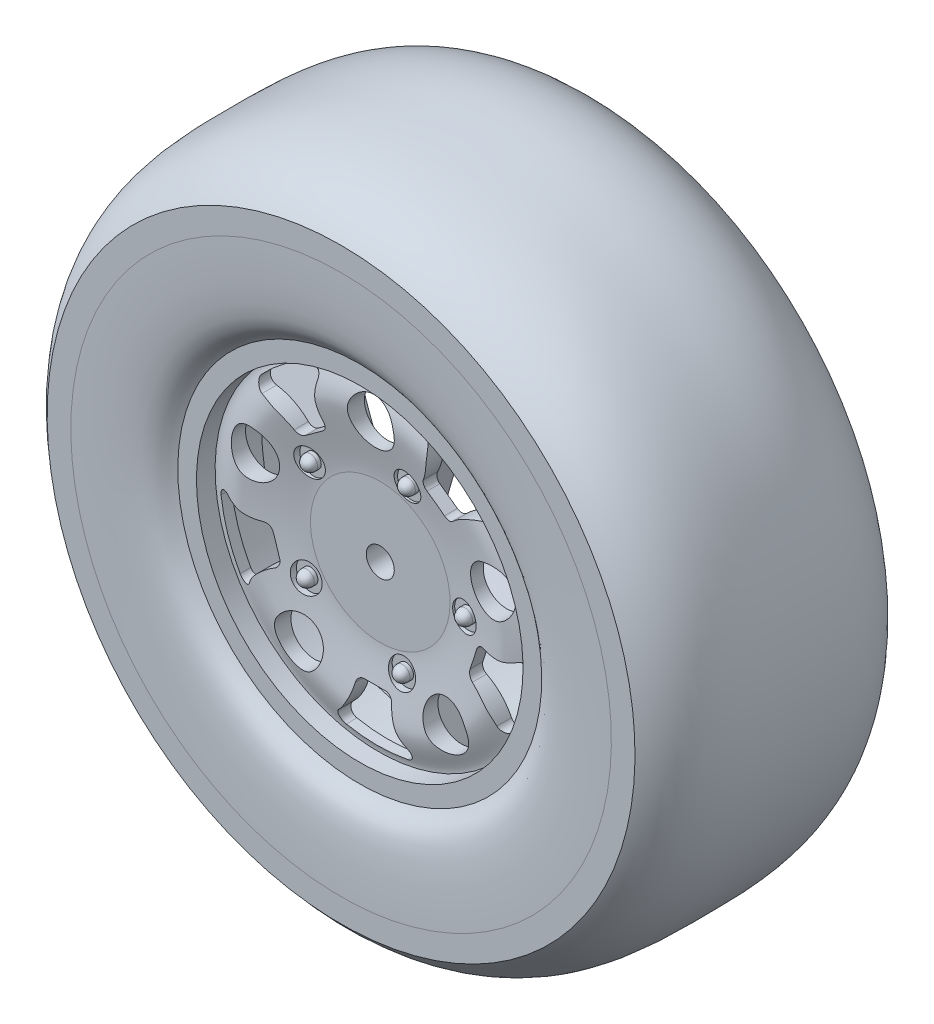
SolidWorks part; units mm, degrees
ref_plane "Front Plane" through (0, 0, 0) normal (0, 0, 1) x (1, 0, 0)
ref_plane "Top Plane" through (0, 0, 0) normal (0, 1, 0) x (1, 0, 0)
ref_plane "Right Plane" through (0, 0, 0) normal (1, 0, 0) x (0, 0, -1)
sketch "Sketch1" plane through (0, 0, 0) normal (1, 0, 0) x (0, 0, -1)
  line L0 (-21.4313, 50.0062) -> (-21.4312, 0)
  line L1 (21.4312, 0) -> (21.4312, 50.0062)
  line L2 (-17.514, 53.4656) -> (17.514, 53.4656) construction
  line L3 (21.4312, 0) -> (-21.4312, 0)
  line L4 (-21.4312, 10.75) -> (21.4312, 10.75) construction
  line L5 (0, 10.75) -> (0, 53.4656) construction
  line L6 (21.4312, 50.0062) -> (26.3997, 50.0062) construction
  line L7 (-18.2562, 30.9562) -> (-18.2562, 27.7812)
  line L8 (-18.2562, 27.7812) -> (-15.0812, 27.7812)
  line L9 (-14.7637, 0) -> (-14.7637, 11.8769)
  line L10 (-14.7637, 2.3812) -> (21.4312, 2.3812)
  line L11 (19.8438, 42.0687) -> (19.8438, 38.8937)
  line L12 (19.8438, 38.8937) -> (-13.4937, 38.8937)
  line L13 (-13.4937, 38.8937) -> (-13.4937, 30.9562)
  line L14 (-13.4937, 30.9562) -> (-5.5562, 30.9562)
  line L15 (-5.5562, 30.9562) -> (-5.5562, 29.3687)
  line L16 (-5.5562, 29.3687) -> (-13.4937, 29.3687)
  line L17 (-13.4937, 29.3687) -> (-13.4937, 5.5562)
  line L18 (-13.4937, 5.5562) -> (-5.5562, 5.5562)
  line L19 (-5.5562, 5.5562) -> (-5.5562, 2.3812)
  spline S0 degree 3 poles (-21.4312, 50.0062) (-16.3365, 56.4478) (0, 56.2647) (16.3365, 56.4478) (21.4312, 50.0062) knots 0 0 0 0 0.5 1 1 1 1
  spline S1 degree 3 poles (-21.4312, 50.0062) (-21.5438, 32.2009) (-20.2763, 33.9382) (-18.2562, 30.9562) knots 0 0 0 0 1 1 1 1
  spline S2 degree 3 poles (-15.0812, 27.7812) (-15.1289, 26.6155) (-16.3602, 24.649) (-16.5049, 21.0048) (-14.8841, 14.5257) (-14.7637, 11.8769) knots 0 0 0 0 0.567974 0.667974 1 1 1 1
  spline S3 degree 3 poles (21.4312, 50.0062) (21.4587, 44.8476) (21.3092, 43.9242) (19.8438, 42.0687) knots 0 0 0 0 1 1 1 1
  dimension "D6" = 19.05
  dimension "D1" = 42.8625
  dimension "D2" = 3.9172
  dimension "D3" = 50.0062
  dimension "D4" = 56.3562
  dimension "D5" = 3.175
  dimension "D7" = 3.175
  dimension "D8" = 3.175
  dimension "D9" = 6.6675
  dimension "D10" = 2.3813
  dimension "D11" = 7.9375
  dimension "D12" = 1.5875
  dimension "D13" = 3.175
  dimension "D14" = 34.925
  dimension "D15" = 1.5875
  dimension "D16" = 7.9375
  dimension "D17" = 5.5562
revolve "Revolve1" add sketch "Sketch1" angle 360 about L3 region at (0, 42.7852, 2.7909)
sketch "Sketch2" plane through (0, 0, 0) normal (0, 0, 1) x (1, 0, 0)
  line L0 (8.8735, 15.3386) -> (11.8459, 13.1791)
  line L1 (10.3597, 14.2588) -> (0, 0) construction
  line L2 (0, 0) -> (0, 9.3337) construction
  line L3 (-12.4986, -17.2029) -> (12.4986, -17.2029) construction
  line L4 (0, 0) -> (20.2232, 6.5709) construction
  circle A0 centre (0, 21.2639) radius 3.9688
  circle A1 centre (20.2232, 6.5709) radius 3.9688
  circle A2 centre (12.4986, -17.2029) radius 3.9688
  circle A3 centre (-12.4986, -17.2029) radius 3.9688
  circle A4 centre (-20.2232, 6.5709) radius 3.9688
  arc A5 (8.4882, 16.9423) -> (9.3812, 22.9129) centre (0, 21.2639) ccw
  arc A6 (11.1644, 3.6275) -> (26.7262, -0.3887) centre (20.2232, 6.5709) ccw
  arc A7 (19.6486, 18.121) -> (11.1624, 24.2867) centre (0, 0) ccw
  arc A8 (-8.6285, 25.298) -> (26.7262, -0.3887) centre (0, 0) ccw
  arc A9 (18.8925, 16.0025) -> (13.4901, 13.3082) centre (20.2232, 6.5709) ccw
  arc A10 (9.3812, 22.9129) -> (11.1624, 24.2867) centre (10.632, 23.1327) cw
  arc A11 (19.6486, 18.121) -> (18.8925, 16.0025) centre (18.7151, 17.26) cw
  arc A12 (13.4901, 13.3082) -> (11.8459, 13.1791) centre (12.5923, 14.2065) cw
  arc A13 (8.8735, 15.3386) -> (8.4882, 16.9423) centre (9.6199, 16.3661) cw
  point P25 (21.3935, 16.0237)
  dimension "D1" = 7.9375
  dimension "D3" = 19.05
  dimension "D4" = 19.05
  dimension "D8" = 1.27
  dimension "D5" = 72
  dimension "D6" = 36
  dimension "D7" = 21.2639
  dimension "D2" = 5
extrude "Cut-Extrude5" cut sketch "Sketch2" along normal up to surface (21.4312 mm away) contours A13 L0 A12 A9 A11 A7 A10 A5 | A0 region at (13.3756, 18.41, 0) region at (0, 21.2639, 0) up to face at (0, 45.9805, 21.4313)
ref_axis "Axis1" through (0, 0, -23.5744) along (0, 0, 1)
pattern_circular "CirPattern1" count 5 over 360 about axis through (0, 0, -23.5744) along (0, 0, 1) of "Cut-Extrude5"
sketch "Sketch5" plane through (0, 0, 14.7638) normal (0, 0, 1) x (1, 0, 0)
  line L0 (0.5332, 3.2628) -> (1.2955, 3.0417)
  line L1 (1.2955, 3.0417) -> (13.9237, 46.5782)
  line L2 (0.5332, 3.2628) -> (13.2791, 47.2052)
  line L3 (13.2791, 47.2052) -> (13.9237, 46.5782)
  line L5 (0.9143, 3.1523) -> (2.5178, 8.6803) construction
  dimension "D1" = 0.7937
extrude "Boss-Extrude2" add sketch "Sketch5" against normal up to surface (9.2075 mm away) up to face at (0, 29.3687, 5.5562)
pattern_circular "CirPattern2" count 5 over 360 about axis through (0, 0, -23.5744) along (0, 0, 1) of "Boss-Extrude2"
sketch "Sketch6" plane through (0, 0, 18.2562) normal (0, 0, 1) x (1, 0, 0)
  circle A0 centre (5.0132, 13.8528) radius 2.3812
  point P2 (0, 0)
  dimension "D1" = 4.7625
  dimension "D2" = 14.732
extrude "Cut-Extrude6" cut sketch "Sketch6" against normal blind 3.81
ref_axis "Axis2" through (5.0132, 13.8528, 14.4462) along (0, 0, 1)
ref_plane "Plane1" through (0, 0, 0) normal (0.9403, -0.3403, 0) x (0, 0, -1)
sketch "Sketch8" plane through (0, 0, 0) normal (0.9403, -0.3403, 0) x (0, 0, -1)
  line L0 (-14.1145, 14.732) -> (-16.3437, 14.732)
  line L2 (-15.0737, 16.002) -> (-14.1145, 16.002)
  line L3 (-14.1145, 16.002) -> (-14.1145, 14.732)
  line L4 (-14.4462, 14.732) -> (-15.6928, 14.732) construction
  arc A0 (-15.0737, 16.002) -> (-16.3437, 14.732) centre (-15.0737, 14.732) ccw
  dimension "D1" = 1.27
revolve "Revolve2" add sketch "Sketch8" angle 360 about L0
pattern_circular "CirPattern3" count 5 over 360 about axis through (0, 0, -23.5744) along (0, 0, 1) of "Revolve2", "Cut-Extrude6"
